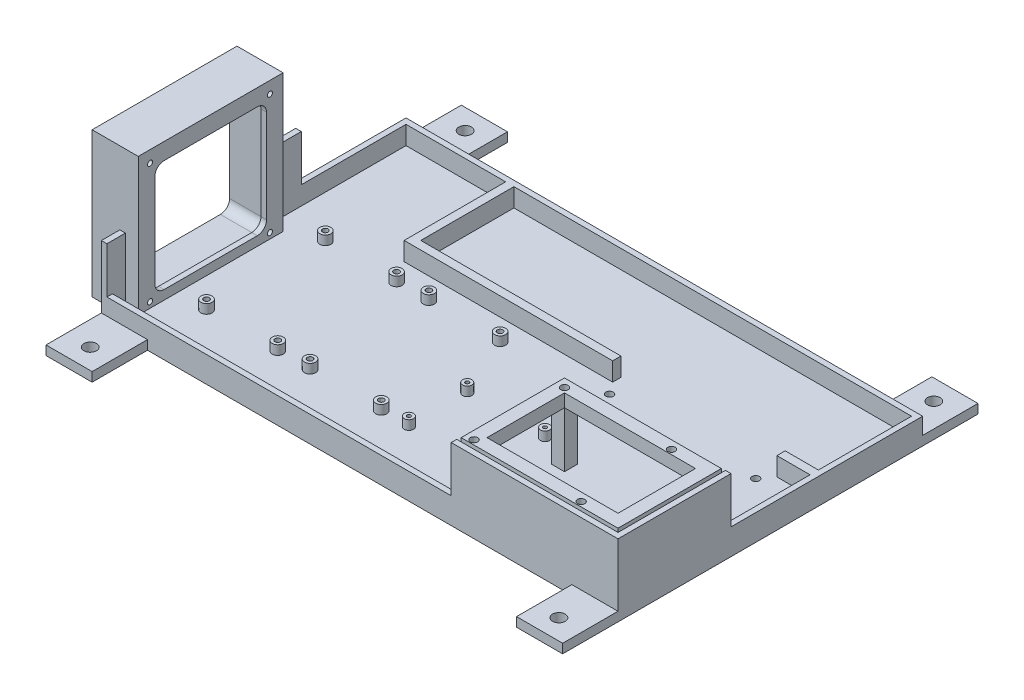
SolidWorks part; units mm, degrees
ref_plane "Front Plane" through (0, 0, 0) normal (0, 0, 1) x (1, 0, 0)
ref_plane "Top Plane" through (0, 0, 0) normal (0, 1, 0) x (1, 0, 0)
ref_plane "Right Plane" through (0, 0, 0) normal (1, 0, 0) x (0, 0, -1)
sketch "Sketch1" plane through (0, 0, 0) normal (0, 1, 0) x (1, 0, 0)
  line L1 (-140, -82.55) -> (140, -82.55)
  line L2 (-140, -82.55) -> (-140, 82.55)
  line L3 (-140, 82.55) -> (140, 82.55)
  line L4 (140, -82.55) -> (140, 82.55)
  line L5 (-140, -82.55) -> (140, 82.55) construction
  line L6 (-140, 82.55) -> (140, -82.55) construction
  point P0 (0, 0)
  dimension "D1" = 165.1
  dimension "D2" = 280
extrude "Floor" add sketch "Sketch1" along normal blind 4
sketch "Sketch2" plane through (0, 4, 0) normal (0, 1, 0) x (1, 0, 0)
  line L0 (137, -79.55) -> (137, 79.55)
  line L1 (137, 79.55) -> (-137, 79.55)
  line L2 (-137, 79.55) -> (-137, -79.55)
  line L3 (-137, -79.55) -> (137, -79.55)
  line L4 (140, -82.55) -> (140, 82.55)
  line L5 (140, 82.55) -> (-140, 82.55)
  line L6 (-140, 82.55) -> (-140, -82.55)
  line L7 (-140, -82.55) -> (140, -82.55)
  line L8 (140, -82.55) -> (140, 82.55)
  line L9 (140, 82.55) -> (-140, 82.55)
  line L10 (-140, 82.55) -> (-140, -82.55)
  line L11 (-140, -82.55) -> (140, -82.55)
  dimension "D1" = 0
  dimension "D2" = 3
extrude "Wall" add sketch "Sketch2" along normal blind 10
sketch "Sketch4" plane through (0, 4, 0) normal (0, 1, 0) x (1, 0, 0)
  line L0 (130, -30.55) -> (59, -30.55)
  line L1 (137, -79.55) -> (52, -79.55)
  line L2 (137, -79.55) -> (137, -23.55)
  line L3 (137, -23.55) -> (52, -23.55)
  line L4 (52, -79.55) -> (52, -23.55)
  line L5 (59, -72.55) -> (59, -30.55)
  line L6 (130, -72.55) -> (59, -72.55)
  line L7 (130, -72.55) -> (130, -30.55)
  dimension "D1" = 85
  dimension "D2" = 56
  dimension "D3" = 7
extrude "Rpi stand" add sketch "Sketch4" along normal blind 7 from offset 30
sketch "Sketch7" plane through (0, 14, 0) normal (0, 1, 0) x (1, 0, 0)
  line L0 (-137, 79.55) -> (-137, -79.55) construction
  line L1 (-140, -82.55) -> (-137, -82.55)
  line L2 (-140, -82.55) -> (-140, 22.7839)
  line L3 (-140, 22.7839) -> (-137, 22.7839)
  line L4 (-137, -82.55) -> (-137, 22.7839)
  line L5 (-137, -79.55) -> (137, -79.55) construction
  line L6 (140, -82.55) -> (49.6123, -82.55)
  line L7 (140, -82.55) -> (140, -79.55)
  line L8 (137, -79.55) -> (49.6123, -79.55)
  line L9 (49.6123, -82.55) -> (49.6123, -79.55)
  line L10 (137, -79.55) -> (137, 79.55) construction
  line L12 (140, -79.55) -> (140, -21.3069)
  line L13 (140, -21.3069) -> (137, -21.3069)
  line L14 (137, -79.55) -> (137, -21.3069)
  line L15 (-137, -79.55) -> (137, -79.55) construction
extrude "Temp support" add sketch "Sketch7" along normal blind 25
sketch "Sketch3" plane through (0, 0, 0) normal (0, 1, 0) x (1, 0, 0)
  line L0 (-127, 101.6) -> (127, 101.6) construction
  line L1 (-140, 82.55) -> (-115, 82.55)
  line L2 (-140, 82.55) -> (-140, 112.55)
  line L3 (-140, 112.55) -> (-115, 112.55)
  line L4 (-115, 82.55) -> (-115, 112.55)
  line L5 (140, 82.55) -> (115, 82.55)
  line L6 (140, 82.55) -> (140, 112.55)
  line L7 (140, 112.55) -> (115, 112.55)
  line L8 (115, 82.55) -> (115, 112.55)
  line L9 (-140, -82.55) -> (-115, -82.55)
  line L10 (-140, -82.55) -> (-140, -112.55)
  line L11 (-140, -112.55) -> (-115, -112.55)
  line L12 (-115, -82.55) -> (-115, -112.55)
  line L13 (140, -82.55) -> (115, -82.55)
  line L14 (140, -82.55) -> (140, -112.55)
  line L15 (140, -112.55) -> (115, -112.55)
  line L16 (115, -82.55) -> (115, -112.55)
  line L17 (127, 101.6) -> (127, -101.6) construction
  line L18 (127, -101.6) -> (-127, -101.6) construction
  line L19 (-127, -101.6) -> (-127, 101.6) construction
  line L20 (-140, 30.6215) -> (140, 30.6215) construction
  line L22 (140, -21.3069) -> (140, 82.55) construction
  line L23 (0, 101.6) -> (0, -101.6) construction
  line L24 (-140, 22.7839) -> (-140, -82.55) construction
  line L25 (140, -21.3069) -> (140, 82.55) construction
  line L26 (-137, -82.55) -> (49.6123, -82.55) construction
  circle A0 centre (-127, 101.6) radius 3.429
  circle A1 centre (127, 101.6) radius 3.429
  circle A2 centre (127, -101.6) radius 3.429
  circle A3 centre (-127, -101.6) radius 3.429
  point P28 (-127.5, -82.55)
  point P29 (-115, -97.55)
  point P30 (127.5, -82.55)
  point P31 (-115, 97.55)
  dimension "D5" = 6.858
  dimension "D1" = 25
  dimension "D2" = 25
  dimension "D3" = 30
  dimension "D4" = 30
  dimension "D6" = 203.2
  dimension "D7" = 254
extrude "Brackets" add sketch "Sketch3" along normal blind 5
sketch "Sketch5" plane through (-140, 0, 0) normal (-1, 0, 0) x (0, 0, 1)
  line L0 (-5.95, 78.5) -> (72.55, 78.5)
  line L1 (3.05, 4) -> (63.55, 4)
  line L2 (-1.95, 9) -> (-1.95, 69.5)
  line L3 (3.05, 74.5) -> (63.55, 74.5)
  line L4 (68.55, 9) -> (68.55, 69.5)
  line L5 (72.55, 0) -> (72.55, 78.5)
  line L6 (-5.95, 0) -> (72.55, 0)
  line L7 (-5.95, 0) -> (-5.95, 78.5)
  line L8 (-1.95, 4) -> (68.55, 4) construction
  line L9 (112.55, 5) -> (112.55, 0) construction
  line L10 (-1.95, 4) -> (-1.95, 74.5) construction
  line L11 (-79.55, 4) -> (79.55, 4) construction
  line L12 (68.55, 4) -> (68.55, 74.5) construction
  line L13 (-1.95, 74.5) -> (68.55, 74.5) construction
  arc A0 (3.05, 4) -> (-1.95, 9) centre (3.05, 9) cw
  arc A1 (63.55, 4) -> (68.55, 9) centre (63.55, 9) ccw
  arc A2 (63.55, 74.5) -> (68.55, 69.5) centre (63.55, 69.5) cw
  arc A3 (-1.95, 69.5) -> (3.05, 74.5) centre (3.05, 69.5) cw
  dimension "D4" = 5
  dimension "D1" = 70.5
  dimension "D2" = 70.5
  dimension "D5" = 40
  dimension "D3" = 4
extrude "Fan Holder" add sketch "Sketch5" along normal blind 15 and the other way blind 10
sketch "Sketch8" plane through (-140, 0, 0) normal (-1, 0, 0) x (0, 0, 1)
  line L4 (-1.95, 39) -> (-1.95, 9)
  line L5 (3.05, 4) -> (63.55, 4)
  line L6 (68.55, 9) -> (68.55, 39)
  line L7 (68.55, 39) -> (-1.95, 39)
  line L8 (-1.95, 39) -> (-1.95, 9)
  line L9 (3.05, 4) -> (63.55, 4)
  line L10 (68.55, 9) -> (68.55, 39)
  line L15 (68.55, 39) -> (-1.95, 39)
  arc A2 (-1.95, 9) -> (3.05, 4) centre (3.05, 9) ccw
  arc A3 (-1.95, 9) -> (3.05, 4) centre (3.05, 9) ccw
  arc A4 (63.55, 4) -> (68.55, 9) centre (63.55, 9) ccw
  arc A5 (63.55, 4) -> (68.55, 9) centre (63.55, 9) ccw
  dimension "D1" = 0
extrude "Fan hole" cut sketch "Sketch8" against normal up to next (3 mm away)
sketch "Sketch11" plane through (-130, 0, 0) normal (-1, 0, 0) x (0, 0, 1)
  line L0 (-5.95, 39.25) -> (72.55, 39.25) construction
  line L1 (33.3, 78.5) -> (33.3, 0) construction
  line L3 (1.1569, 7.0548) -> (66.1569, 7.0548) construction
  line L4 (-5.95, 78.5) -> (-5.95, 0)
  line L5 (-5.95, 0) -> (72.55, 0)
  line L6 (72.55, 0) -> (72.55, 78.5)
  line L7 (72.55, 78.5) -> (-5.95, 78.5)
  line L8 (-5.95, 78.5) -> (-5.95, 0)
  line L9 (-5.95, 0) -> (72.55, 0)
  line L10 (72.55, 0) -> (72.55, 78.5)
  line L11 (72.55, 78.5) -> (-5.95, 78.5)
  line L12 (1.1569, 7.0548) -> (1.1569, 72.0548) construction
  line L13 (1.1569, 72.0548) -> (66.1569, 72.0548) construction
  line L14 (66.1569, 7.0548) -> (66.1569, 72.0548) construction
  line L15 (1.1569, 7.0548) -> (66.1569, 72.0548) construction
  line L16 (3.05, 69.5) -> (3.05, 9)
  line L17 (3.05, 9) -> (63.55, 9)
  line L18 (63.55, 9) -> (63.55, 69.5)
  line L19 (63.55, 69.5) -> (3.05, 69.5)
  line L20 (3.05, 64.5) -> (3.05, 14)
  line L21 (8.05, 9) -> (58.55, 9)
  line L22 (63.55, 14) -> (63.55, 64.5)
  line L23 (58.55, 69.5) -> (8.05, 69.5)
  line L24 (1.1569, 72.0548) -> (66.1569, 7.0548) construction
  arc A0 (3.05, 14) -> (8.05, 9) centre (8.05, 14) ccw
  arc A1 (58.55, 9) -> (63.55, 14) centre (58.55, 14) ccw
  arc A2 (63.55, 64.5) -> (58.55, 69.5) centre (58.55, 64.5) ccw
  arc A3 (3.05, 64.5) -> (8.05, 69.5) centre (8.05, 64.5) cw
  circle A4 centre (1.1569, 72.0548) radius 1.3864
  circle A5 centre (66.1569, 72.0548) radius 1.3864
  circle A6 centre (66.1569, 7.0548) radius 1.3864
  circle A7 centre (1.1569, 7.0548) radius 1.3864
  point P24 (33.6569, 39.5548)
  dimension "D3" = 5
  dimension "D4" = 65
  dimension "D5" = 65
  dimension "D1" = 0
  dimension "D2" = 9
extrude "Boss-Extrude9" add sketch "Sketch11" along normal blind 3
sketch "Sketch12" plane through (0, 34, 0) normal (0, -1, 0) x (1, 0, 0)
  line L1 (52, 23.55) -> (59, 23.55)
  line L2 (52, 23.55) -> (52, 30.55)
  line L3 (52, 30.55) -> (59, 30.55)
  line L4 (59, 23.55) -> (59, 30.55)
  dimension "D1" = 7
  dimension "D2" = 7
extrude "Boss-Extrude10" add sketch "Sketch12" along normal up to next
sketch "Sketch13" plane through (0, 4, 0) normal (0, 1, 0) x (1, 0, 0)
  line L0 (-137, -79.55) -> (137, -79.55) construction
  line L1 (-137, -82.55) -> (-137, -72.55) construction
  line L2 (-114, -51.55) -> (-114, 12.85) construction
  line L3 (-114, 12.85) -> (-75.4, 12.85) construction
  line L4 (-114, -51.55) -> (-75.4, -51.55) construction
  line L5 (-75.4, 12.85) -> (-75.4, -51.55) construction
  line L6 (-75.4, 12.85) -> (-57.9, 12.85) construction
  line L7 (-57.9, 12.85) -> (-57.9, -51.55) construction
  line L8 (-57.9, -51.55) -> (-19.3, -51.55) construction
  line L9 (-19.3, -51.55) -> (-19.3, 12.85) construction
  line L10 (-19.3, 12.85) -> (-57.9, 12.85) construction
  line L11 (-75.4, -51.55) -> (-57.9, -51.55) construction
  line L12 (-19.3, -51.55) -> (-4.3, -51.55) construction
  line L13 (-4.3, -51.55) -> (-4.3, -19.95) construction
  line L14 (-4.3, -19.95) -> (37.87, -19.95) construction
  line L15 (37.87, -19.95) -> (37.87, -51.55) construction
  line L16 (37.87, -51.55) -> (-4.3, -51.55) construction
  line L17 (111.34, 79.55) -> (111.34, 18.05) construction
  line L19 (137, 79.55) -> (-137, 79.55) construction
  line L20 (137, -21.3069) -> (137, 79.55) construction
  line L21 (111.34, 18.05) -> (114.04, 18.05) construction
  line L22 (111.34, 18.05) -> (34.84, 18.05) construction
  circle A0 centre (-114, -51.55) radius 1.5
  circle A1 centre (-114, 12.85) radius 1.5
  circle A2 centre (-75.4, 12.85) radius 1.5
  circle A3 centre (-75.4, -51.55) radius 1.5
  circle A4 centre (-57.9, 12.85) radius 1.5
  circle A5 centre (-57.9, -51.55) radius 1.5
  circle A6 centre (-19.3, -51.55) radius 1.5
  circle A7 centre (-19.3, 12.85) radius 1.5
  circle A8 centre (-4.3, -51.55) radius 1
  circle A9 centre (-4.3, -19.95) radius 1
  circle A10 centre (37.87, -19.95) radius 1
  circle A11 centre (37.87, -51.55) radius 1
  circle A12 centre (114.04, 18.05) radius 2
  circle A13 centre (34.84, 18.05) radius 2
  circle A14 centre (-114, 12.85) radius 3
  circle A15 centre (-114, -51.55) radius 3
  circle A16 centre (-75.4, 12.85) radius 3
  circle A17 centre (-57.9, 12.85) radius 3
  circle A18 centre (-75.4, -51.55) radius 3
  circle A19 centre (-57.9, -51.55) radius 3
  circle A20 centre (-19.3, -51.55) radius 3
  circle A21 centre (-19.3, 12.85) radius 3
  circle A22 centre (-4.3, -51.55) radius 2.5
  circle A23 centre (-4.3, -19.95) radius 2.5
  circle A24 centre (37.87, -19.95) radius 2.5
  circle A25 centre (37.87, -51.55) radius 2.5
  point P6 (-137, -77.55)
  dimension "D1" = 28
  dimension "D2" = 23
  dimension "D3" = 3
  dimension "D6" = 3
  dimension "D7" = 3
  dimension "D8" = 3
  dimension "D11" = 3
  dimension "D12" = 3
  dimension "D13" = 3
  dimension "D14" = 3
  dimension "D16" = 2
  dimension "D18" = 2
  dimension "D20" = 2
  dimension "D21" = 2
  dimension "D25" = 4
  dimension "D27" = 4
  dimension "D4" = 64.4
  dimension "D5" = 38.6
  dimension "D9" = 17.5
  dimension "D10" = 38.6
  dimension "D15" = 15
  dimension "D17" = 31.6
  dimension "D19" = 42.17
  dimension "D22" = 61.5
  dimension "D23" = 25.66
  dimension "D24" = 2.7
  dimension "D26" = 76.5
  dimension "D28" = 1.5
extrude "Boss-Extrude12" add sketch "Sketch13" along normal blind 5 contours A1 | A16 A2 | A2 | A17 A4 | A4 | A14 A1 | A21 A7 | A7 | A15 A0 | A0 | A18 A3 | A3 | A19 A5 | A5 | A20 A6 | A6 | A22 A8 | A8 | A23 A9 | A9 | A24 A10 | A10 | A25 A11 | A11 region at (-114, 4, 51.55) region at (-114, 4, -12.85) region at (-75.4, 4, -12.85) region at (-75.4, 4, 51.55) region at (-57.9, 4, -12.85) region at (-57.9, 4, 51.55) region at (-19.3, 4, 51.55) region at (-19.3, 4, -12.85) region at (-4.3, 4, 51.55) region at (-4.3, 4, 19.95) region at (37.87, 4, 19.95) region at (37.87, 4, 51.55) region at (-116.9151, 4, -12.85) region at (-116.9151, 4, 51.55) region at (-78.3151, 4, -12.85) region at (-60.8151, 4, -12.85) region at (-78.3151, 4, 51.55) region at (-60.8151, 4, 51.55) region at (-22.2151, 4, 51.55) region at (-22.2151, 4, -12.85) region at (-6.7293, 4, 51.55) region at (-6.7293, 4, 19.95) region at (35.4407, 4, 19.95) region at (35.4407, 4, 51.55)
sketch "Sketch14" plane through (0, 4, 0) normal (0, 1, 0) x (1, 0, 0)
  line L0 (137, 79.55) -> (-78, 79.55)
  line L1 (137, 79.55) -> (-137, 79.55) construction
  line L2 (-78, 79.55) -> (-78, 29.55)
  line L3 (-78, 29.55) -> (137, 29.55)
  line L4 (137, -79.55) -> (137, 79.55) construction
  line L5 (137, 29.55) -> (137, 79.55)
  dimension "D1" = 215
  dimension "D2" = 50
extrude "Cut-Extrude1" cut sketch "Sketch13<4>" against normal blind 5 from surface contours A1 | A0 | A3 | A5 | A2 | A4 | A7 | A9 | A8 | A6 | A11 | A10 starting at face at (-114, 9, -9.85)
sketch "Sketch13<4>" plane through (0, 4, 0) normal (0, 1, 0) x (1, 0, 0) same geometry as "Sketch13"
extrude "Cut-Extrude2" cut sketch "Sketch13<5>" against normal blind 3 contours A13 | A12
sketch "Sketch13<5>" plane through (0, 4, 0) normal (0, 1, 0) x (1, 0, 0) same geometry as "Sketch13"
sketch "Sketch16" plane through (0, 4, 0) normal (0, 1, 0) x (1, 0, 0)
  line L0 (-83, 79.55) -> (-83, 24.55)
  line L1 (-83, 24.55) -> (30, 24.55)
  line L2 (-78.5, 79.55) -> (-78.5, 29.05)
  line L3 (-78.5, 29.05) -> (30, 29.05)
  line L10 (-78, 79.55) -> (-78, 29.55) construction
  line L11 (-78, 29.55) -> (29.1074, 29.55) construction
  line L12 (119, 24.55) -> (137, 24.55)
  line L13 (119, 29.55) -> (137, 29.55) construction
  line L14 (-83, 24.55) -> (137, 24.55) construction
  line L15 (119, 29.05) -> (137, 29.05)
  line L16 (-78, 29.55) -> (137, 29.55) construction
  line L17 (-78.5, 79.55) -> (-83, 79.55)
  line L18 (119, 29.05) -> (119, 24.55)
  line L19 (137, -21.3069) -> (137, 79.55) construction
  line L20 (30, 24.55) -> (30, 29.05)
  line L21 (-78.5, 29.05) -> (29.1074, 29.05) construction
  line L22 (137, 24.55) -> (137, 29.05)
  line L25 (-78, 29.55) -> (137, 29.55)
  line L26 (137, 29.55) -> (137, 79.55)
  line L27 (137, 79.55) -> (-78, 79.55)
  line L28 (-78, 79.55) -> (-78, 29.55)
  line L29 (-78, 29.55) -> (137, 29.55) construction
  line L30 (137, 29.55) -> (137, 79.55) construction
  line L31 (137, 79.55) -> (-78, 79.55) construction
  line L32 (-78, 79.55) -> (-78, 29.55) construction
  dimension "D3" = 0.5
  dimension "D4" = 18
  dimension "D5" = 113
  dimension "D1" = 0
  dimension "D2" = 5
extrude "Boss-Extrude11" add sketch "Sketch16" along normal blind 10 contours L2 L3 L20 L1 L0 L17 | L12 L22 L15 L18
sketch "Sketch17" plane through (0, 41, 0) normal (0, 1, 0) x (1, 0, 0)
  circle A0 centre (56.5, -28.05) radius 2
  circle A1 centre (114.5, -28.05) radius 2
  circle A2 centre (114.5, -77.05) radius 2
  circle A3 centre (56.5, -77.05) radius 2
  dimension "D1" = 4
extrude "Cut-Extrude3" cut sketch "Sketch17" against normal blind 3
equation "\"D2@Sketch3\"=\"D1@Sketch3\""
equation "\"D4@Sketch3\"=\"D3@Sketch3\""
